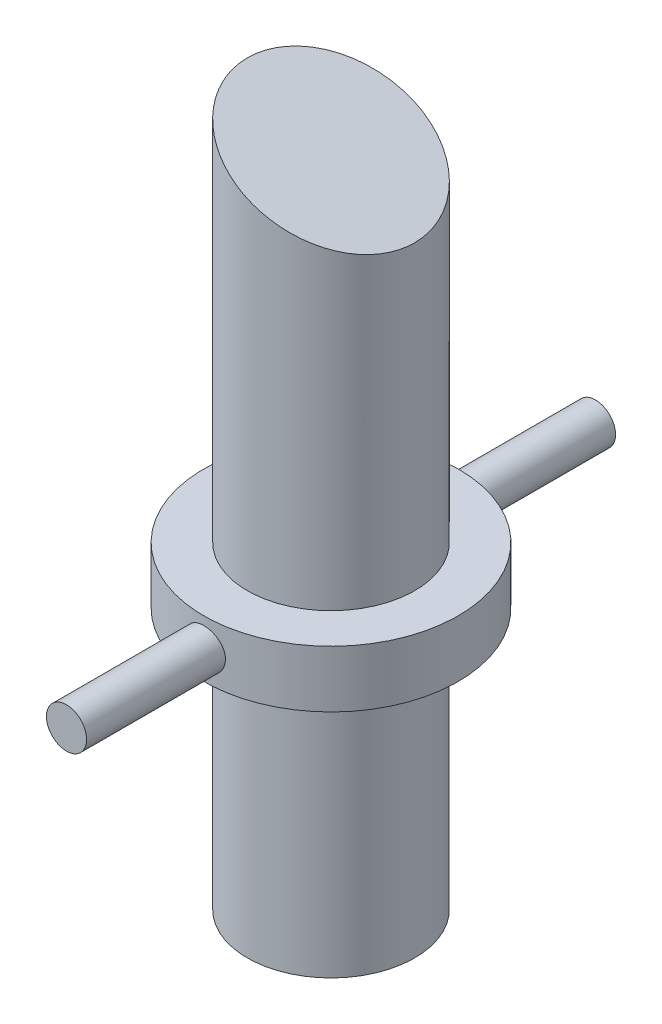
SolidWorks part; units mm, degrees
ref_plane "Front" through (0, 0, 0) normal (0, 0, 1) x (1, 0, 0)
ref_plane "Top" through (0, 0, 0) normal (0, 1, 0) x (1, 0, 0)
ref_plane "Right" through (0, 0, 0) normal (1, 0, 0) x (0, 0, -1)
sketch "Sketch1" plane through (0, 0, 0) normal (0, 0, 1) x (1, 0, 0)
  line L0 (0, 0) -> (0, 207.8393)
  line L1 (0, 207.8393) -> (25, 207.8393)
  line L2 (25, 207.8393) -> (25, 95)
  line L3 (25, 95) -> (38, 95)
  line L4 (38, 95) -> (38, 78)
  line L5 (38, 78) -> (25, 78)
  line L6 (25, 78) -> (25, 0)
  line L7 (25, 0) -> (0, 0)
  dimension "D1" = 25
  dimension "D2" = 25
  dimension "D3" = 78
  dimension "D4" = 17
  dimension "D5" = 38
revolve "Revolve1" add sketch "Sketch1" angle 360 about L0
sketch "Sketch2" plane through (0, 0, 0) normal (0, 0, 1) x (1, 0, 0)
  line L0 (-25, 207.8393) -> (25, 185)
  line L1 (25, 95) -> (25, 207.8393) construction
  line L2 (38, 95) -> (-38, 95) construction
  dimension "D1" = 90
extrude "Cut-Extrude1" cut sketch "Sketch2" against normal through all and the other way through all
sketch "Sketch5" plane through (0, 0, 0) normal (0, 0, 1) x (1, 0, 0)
  line L0 (0, 95) -> (0, 78) construction
  line L1 (38, 95) -> (-38, 95) construction
  circle A0 centre (0, 86.5) radius 6
  dimension "D1" = 12
  dimension "D2" = 8.5
extrude "Boss-Extrude1" add sketch "Sketch5" along normal blind 79
sketch "Sketch6" plane through (0, 0, 0) normal (0, 0, 1) x (1, 0, 0)
  line L0 (0, 95) -> (0, 78) construction
  circle A0 centre (0, 86.354) radius 6
  dimension "D1" = 12
extrude "Boss-Extrude3" add sketch "Sketch6" against normal blind 79
